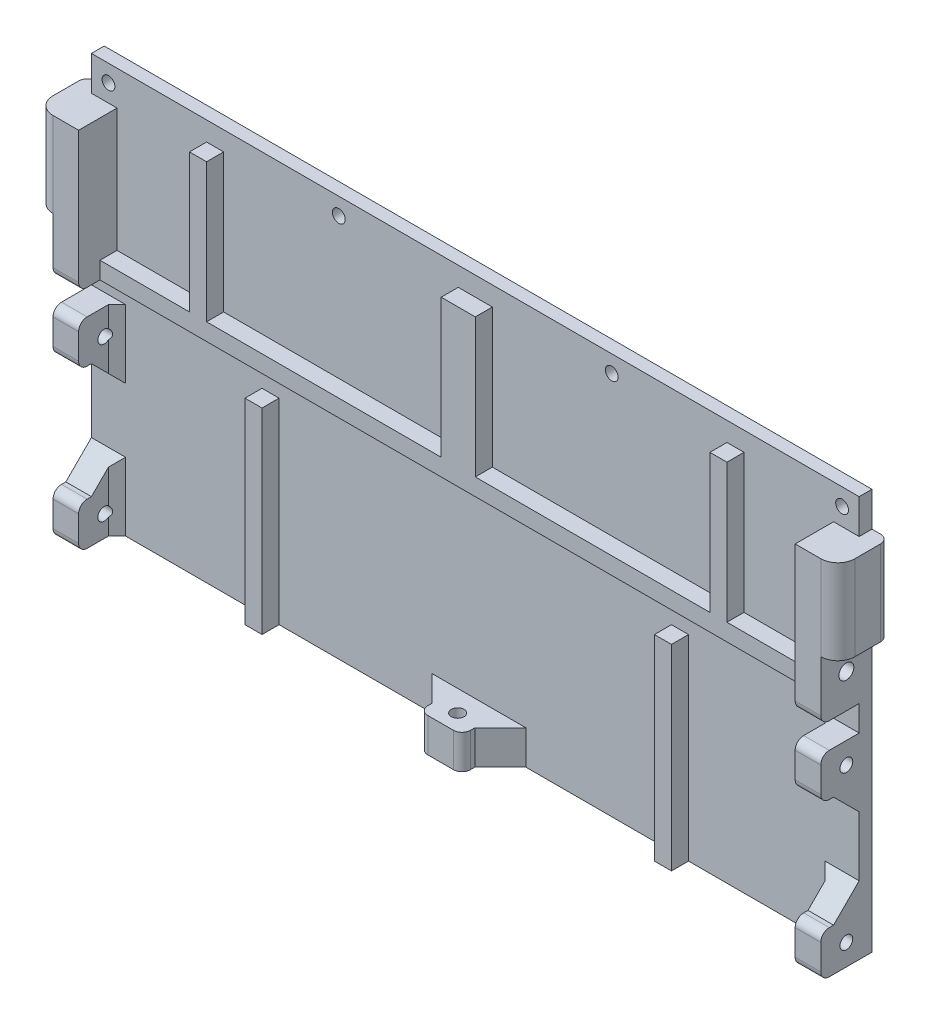
SolidWorks part; units mm, degrees
material "АБС-2020, черный"
ref_plane "Спереди" through (0, 0, 0) normal (0, 0, 1) x (1, 0, 0)
ref_plane "Сверху" through (0, 0, 0) normal (0, 1, 0) x (1, 0, 0)
ref_plane "Справа" through (0, 0, 0) normal (1, 0, 0) x (0, 0, -1)
other "Configuration Table"
sketch "Эскиз1" plane through (0, 0, 0) normal (0, 0, 1) x (1, 0, 0)
  line L1 (0, 0) -> (180, 0)
  line L2 (0, 0) -> (0, -94)
  line L3 (0, -94) -> (180, -94)
  line L4 (180, 0) -> (180, -94)
  dimension "D1" = 94
  dimension "D2" = 180
extrude "Бобышка-Вытянуть1" add sketch "Эскиз1" along normal blind 3
sketch "Эскиз2" plane through (0, 0, 3) normal (0, 0, 1) x (1, 0, 0)
  line L0 (0, 0) -> (0, -94) construction
  line L1 (0, -94) -> (6, -94)
  line L2 (0, -94) -> (0, -84)
  line L3 (0, -84) -> (6, -84)
  line L4 (6, -94) -> (6, -84)
  line L5 (180, -94) -> (174, -94)
  line L6 (180, -94) -> (180, -84)
  line L7 (180, -84) -> (174, -84)
  line L8 (174, -94) -> (174, -84)
  line L9 (0, -47) -> (6, -47)
  line L10 (0, -47) -> (0, -57)
  line L11 (0, -57) -> (6, -57)
  line L12 (6, -47) -> (6, -57)
  line L13 (180, -94) -> (180, 0) construction
  line L14 (180, -48) -> (174, -48)
  line L15 (180, -48) -> (180, -58)
  line L16 (180, -58) -> (174, -58)
  line L17 (174, -48) -> (174, -58)
  line L18 (0, -94) -> (180, -94) construction
  line L19 (180, 0) -> (0, 0) construction
  line L20 (180, -8.1) -> (174, -8.1)
  line L21 (180, -8.1) -> (180, -42)
  line L22 (180, -42) -> (174, -42)
  line L23 (174, -8.1) -> (174, -42)
  line L24 (0, -8.1) -> (6, -8.1)
  line L25 (0, -8.1) -> (0, -41)
  line L26 (0, -41) -> (6, -41)
  line L27 (6, -8.1) -> (6, -41)
  line L29 (85.876, -94) -> (95.876, -94)
  line L30 (85.876, -94) -> (85.876, -86)
  line L31 (85.876, -86) -> (95.876, -86)
  line L32 (95.876, -94) -> (95.876, -86)
  point P28 (3, -41)
  point P39 (0, 0)
  point P40 (90.876, -94)
  dimension "D1" = 10
  dimension "D2" = 6
  dimension "D3" = 10
  dimension "D4" = 6
  dimension "D5" = 46
  dimension "D6" = 6
  dimension "D7" = 6
  dimension "D8" = 47
  dimension "D9" = 10
  dimension "D10" = 10
  dimension "D11" = 6
  dimension "D12" = 8.1
  dimension "D13" = 8.1
  dimension "D14" = 6
  dimension "D15" = 10
  dimension "D16" = 5
  dimension "D17" = 8
extrude "Бобышка-Вытянуть2" add sketch "Эскиз2" along normal blind 9
chamfer "Фаска2" distance 6 angle 45 2 edges at (3, -57, 3) (177, -58, 3)
chamfer "Фаска1" distance 6 angle 45 2 edges at (3, -84, 3) (177, -84, 3)
sketch "Эскиз3" plane through (180, 0, 0) normal (1, 0, 0) x (0, 0, -1)
  line L0 (0, -94) -> (0, 0) construction
  line L1 (-12, -94) -> (0, -94) construction
  line L2 (-3, 0) -> (0, 0) construction
  circle A0 centre (-6, -89) radius 1.5
  circle A1 centre (-6, -53) radius 1.5
  circle A2 centre (-6, -34) radius 1.75
  dimension "D1" = 3
  dimension "D4" = 3
  dimension "D7" = 3.5
  dimension "D2" = 6
  dimension "D3" = 5
  dimension "D5" = 36
  dimension "D6" = 34
extrude "Вырез-Вытянуть1" cut sketch "Эскиз3" against normal up to next
sketch "Эскиз4" plane through (0, 0, 3) normal (0, 0, 1) x (1, 0, 0)
  line L0 (0, -84) -> (0, -94) construction
  line L1 (180, -94) -> (180, -84) construction
  line L2 (180, 0) -> (0, 0) construction
  circle A0 centre (4, -4) radius 1.5
  circle A1 centre (176, -4) radius 1.5
  circle A2 centre (58, -4) radius 1.5
  circle A3 centre (122, -4) radius 1.5
  dimension "D7" = 3
  dimension "D4" = 3
  dimension "D5" = 3
  dimension "D1" = 4
  dimension "D2" = 4
  dimension "D3" = 4
  dimension "D6" = 54
  dimension "D8" = 54
extrude "Вырез-Вытянуть2" cut sketch "Эскиз4" against normal through all
sketch "Эскиз5" plane through (0, 0, 3) normal (0, 0, 1) x (1, 0, 0)
  line L0 (6, -94) -> (85.876, -94) construction
  line L1 (40, -48) -> (44, -48)
  line L2 (40, -48) -> (40, -94)
  line L3 (40, -94) -> (44, -94)
  line L4 (44, -48) -> (44, -94)
  line L5 (180, -78) -> (180, -64) construction
  line L6 (136, -48) -> (140, -48)
  line L7 (136, -48) -> (136, -94)
  line L8 (136, -94) -> (140, -94)
  line L9 (140, -48) -> (140, -94)
  line L10 (0, -63) -> (0, -78) construction
  line L11 (180, 0) -> (0, 0) construction
  line L13 (27, -4.5) -> (27, -37)
  line L15 (31, -4.5) -> (31, -37)
  line L18 (149, -4.5) -> (149, -37)
  line L20 (153, -4.5) -> (153, -37)
  line L21 (27, -4.5) -> (31, -4.5)
  line L22 (149, -4.5) -> (153, -4.5)
  line L23 (0, 0) -> (0, -8.1) construction
  line L24 (180, -48) -> (180, -42) construction
  line L25 (174, -8.1) -> (174, -42) construction
  line L26 (86, -4.5) -> (94, -4.5)
  line L27 (86, -4.5) -> (86, -37)
  line L29 (94, -4.5) -> (94, -37)
  line L31 (6, -41) -> (6, -37)
  line L32 (6, -37) -> (27, -37)
  line L33 (174, -41) -> (174, -37)
  line L34 (31, -37) -> (86, -37)
  line L35 (94, -37) -> (149, -37)
  line L36 (153, -37) -> (174, -37)
  line L37 (6, -41) -> (174, -41)
  dimension "D12" = 8
  dimension "D1" = 4
  dimension "D2" = 4
  dimension "D3" = 40
  dimension "D4" = 40
  dimension "D7" = 27
  dimension "D8" = 4
  dimension "D9" = 4.5
  dimension "D10" = 4
  dimension "D11" = 27
  dimension "D13" = 55
  dimension "D14" = 55
  dimension "D15" = 46
  dimension "D16" = 46
extrude "Бобышка-Вытянуть3" add sketch "Эскиз5" along normal blind 4
chamfer "Фаска3" distance 2 angle 45 4 edges at (174, -86, 3) (174, -56, 3) (6, -86, 3) (6, -55, 3)
sketch "Эскиз6" plane through (180, 0, 0) normal (1, 0, 0) x (0, 0, -1)
  line L0 (0, -94) -> (0, 0) construction
  line L1 (-12, -8.1) -> (0, -8.1)
  line L2 (-12, -8.1) -> (-12, -28)
  line L3 (-12, -28) -> (0, -28)
  line L4 (0, -8.1) -> (0, -28)
  line L5 (-3, 0) -> (0, 0) construction
  dimension "D1" = 28
  dimension "D2" = 8.1
extrude "Бобышка-Вытянуть4" add sketch "Эскиз6" along normal blind 4
fillet "Скругление1" radius 4 1 edges at (184, -18.05, 12)
sketch "Эскиз7" plane through (0, 0, 0) normal (-1, 0, 0) x (0, 0, 1)
  line L0 (12, -8.1) -> (12, -41) construction
  line L1 (0, -8.1) -> (12, -8.1)
  line L2 (0, -8.1) -> (0, -28)
  line L3 (0, -28) -> (12, -28)
  line L4 (12, -8.1) -> (12, -28)
  line L5 (3, 0) -> (0, 0) construction
  dimension "D1" = 28
extrude "Бобышка-Вытянуть5" add sketch "Эскиз7" along normal blind 4
fillet "Скругление2" radius 4 1 edges at (-4, -18.05, 12)
fillet "Скругление3" radius 2 2 edges at (184, -18.05, 0) (-4, -18.05, 0)
sketch "Эскиз8" plane through (0, -94, 0) normal (0, -1, 0) x (1, 0, 0)
  line L0 (95.876, 3) -> (136, 3) construction
  line L1 (85.876, 12) -> (85.876, 3) construction
  circle A0 centre (90.876, 8) radius 1.5
  dimension "D3" = 3
  dimension "D1" = 5
  dimension "D2" = 5
extrude "Вырез-Вытянуть3" cut sketch "Эскиз8" against normal blind 10
sketch "Эскиз9" plane through (0, 0, 0) normal (-1, 0, 0) x (0, 0, 1)
  line L0 (0, -28) -> (0, -94) construction
  line L1 (12, -94) -> (0, -94) construction
  circle A0 centre (6, -89) radius 1.5
  circle A1 centre (6, -53) radius 1.5
  point P8 (0, 0)
  dimension "D1" = 3
  dimension "D2" = 3
  dimension "D3" = 36
  dimension "D4" = 6
  dimension "D5" = 5
extrude "Вырез-Вытянуть4" cut sketch "Эскиз9" against normal up to next
chamfer "Фаска4" distance 6 angle 45 2 edges at (95.876, -90, 3) (85.876, -90, 3)
fillet "Скругление4" radius 2 12 edges at (177, -84, 12) (3, -84, 12) (3, -41, 12) (3, -47, 12) (3, -57, 12) (3, -94, 12) (177, -42, 12) (177, -48, 12) (177, -58, 12) (85.876, -90, 12) (95.876, -90, 12) (177, -94, 12)
